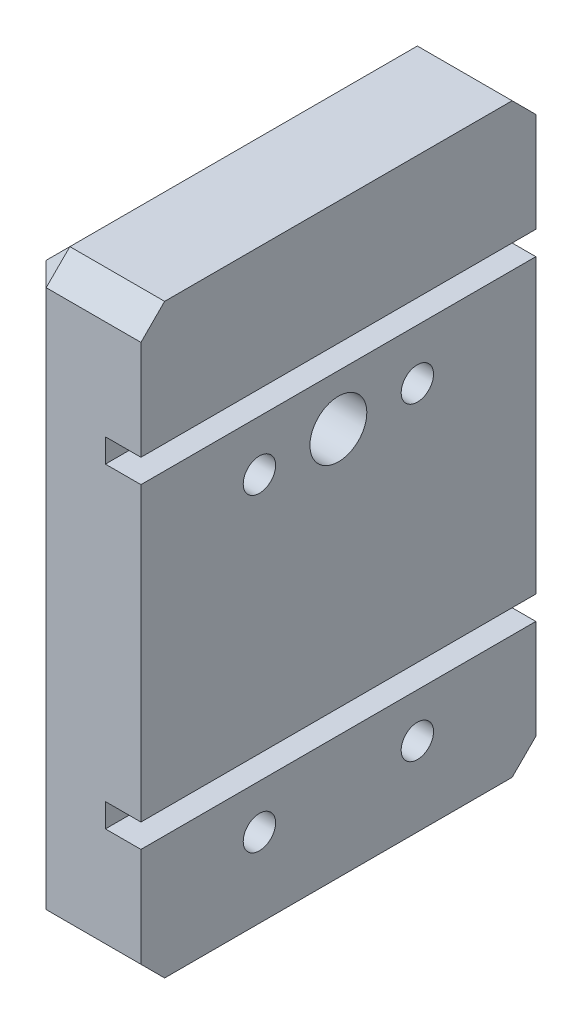
SolidWorks part; units mm, degrees
ref_plane "Front Plane" through (0, 0, 0) normal (0, 0, 1) x (1, 0, 0)
ref_plane "Top Plane" through (0, 0, 0) normal (0, 1, 0) x (1, 0, 0)
ref_plane "Right Plane" through (0, 0, 0) normal (1, 0, 0) x (0, 0, -1)
sketch "Sketch1" plane through (0, 0, 0) normal (0, 0, 1) x (1, 0, 0)
  line L2 (0, 0) -> (0, -74.2)
  line L10 (-15, -74.2) -> (-15, 0)
  line L12 (-15, 0) -> (0, 0)
  line L13 (0, -74.2) -> (-15, -74.2)
  point P0 (0, 0)
  dimension "D1" = 15
  dimension "D2" = 74.2
extrude "Boss-Extrude1" add sketch "Sketch1" along normal blind 50
sketch "Sketch4" plane through (-15, 0, 0) normal (-1, 0, 0) x (0, 0, 1)
  line L0 (0, 0) -> (50, -50) construction
  line L1 (50, 0) -> (50, -74.2) construction
  line L3 (50, 0) -> (0, 0) construction
  circle A0 centre (25, -25) radius 18 construction
  circle A1 centre (43, -25) radius 2.5
  circle A2 centre (41.2174, -32.8099) radius 2.5
  circle A3 centre (36.2228, -39.073) radius 2.5
  circle A4 centre (29.0054, -42.5487) radius 2.5
  circle A5 centre (20.9946, -42.5487) radius 2.5
  circle A6 centre (13.7772, -39.073) radius 2.5
  circle A7 centre (8.7826, -32.8099) radius 2.5
  circle A8 centre (7, -25) radius 2.5
  circle A9 centre (8.7826, -17.1901) radius 2.5
  circle A10 centre (13.7772, -10.927) radius 2.5
  circle A11 centre (20.9946, -7.4513) radius 2.5
  circle A12 centre (29.0054, -7.4513) radius 2.5
  circle A13 centre (36.2228, -10.927) radius 2.5
  circle A14 centre (41.2174, -17.1901) radius 2.5
  dimension "D2" = 5
  dimension "D4" = 36
  dimension "D1" = 45
  dimension "D5" = 25.714
  dimension "D3" = 14
extrude "Cut-Extrude4" cut sketch "Sketch4" against normal blind 4
chamfer "Chamfer2" distance 0.8 angle 45 14 edges at (-15, -27.5, 43) (-15, -19.6901, 41.2174) (-15, -13.427, 36.2228) (-15, -9.9513, 29.0054) (-15, -9.9513, 20.9946) (-15, -13.427, 13.7772) (-15, -19.6901, 8.7826) (-15, -27.5, 7) (-15, -35.3099, 8.7826) (-15, -41.573, 13.7772) (-15, -45.0487, 20.9946) (-15, -45.0487, 29.0054) (-15, -35.3099, 41.2174) (-15, -41.573, 36.2228)
sketch "Sketch5" plane through (-15, 0, 0) normal (-1, 0, 0) x (0, 0, 1)
  line L0 (13.7772, -39.073) -> (36.2228, -10.927) construction
  circle A0 centre (25, -25) radius 3.6
  dimension "D1" = 7.2
extrude "Cut-Extrude5" cut sketch "Sketch5" against normal up to surface (15 mm away) up to face at (0, -37.1, 25)
chamfer "Chamfer3" distance 1.5 angle 45 1 edges at (-15, -28.6, 25)
sketch "Sketch6" plane through (0, 0, 50) normal (0, 0, 1) x (1, 0, 0)
  line L0 (0, -74.2) -> (0, 0) construction
  line L1 (0, -15.6) -> (-4.5, -15.6)
  line L2 (0, -15.6) -> (0, -18.6)
  line L3 (0, -18.6) -> (-4.5, -18.6)
  line L4 (-4.5, -15.6) -> (-4.5, -18.6)
  line L9 (0, -37.1) -> (-15, -37.1) construction
  line L10 (-15, 0) -> (-15, -74.2) construction
  line L15 (-4.5, -58.6) -> (-4.5, -55.6)
  line L16 (0, -55.6) -> (-4.5, -55.6)
  line L17 (0, -58.6) -> (0, -55.6)
  line L18 (0, -58.6) -> (-4.5, -58.6)
  point P4 (-4.5, -17.1)
  point P5 (-4.5, -57.1)
  dimension "D1" = 3
  dimension "D2" = 40
  dimension "D3" = 4.5
extrude "Cut-Extrude6" cut sketch "Sketch6" against normal up to surface (50 mm away) up to face at (-7.5, -37.1, 0)
sketch "Sketch7" plane through (-15, 0, 0) normal (-1, 0, 0) x (0, 0, 1)
  line L0 (25, -35.2) -> (25, -74.2) construction
  line L1 (50, -74.2) -> (0, -74.2) construction
  line L2 (25, -25) -> (50, -25) construction
  line L3 (50, 0) -> (50, -74.2) construction
  circle A0 centre (15, -64.2) radius 3.75
  circle A1 centre (35, -64.2) radius 3.75
  circle A3 centre (15, -25) radius 3.75
  circle A4 centre (35, -25) radius 3.75
  point P18 (0, 0)
  point P19 (0, 0)
  point P20 (0, 0)
  dimension "D1" = 7.5
  dimension "D3" = 10
  dimension "D2" = 20
  dimension "D4" = 10
  dimension "D5" = 39.2
extrude "Cut-Extrude7" cut sketch "Sketch7" against normal blind 5
sketch "Sketch8" plane through (-10, 0, 0) normal (-1, 0, 0) x (0, 0, 1)
  circle A0 centre (35, -64.2) radius 2.05
  circle A1 centre (15, -64.2) radius 2.05
  circle A3 centre (15, -25) radius 2.05
  circle A4 centre (35, -25) radius 2.05
  dimension "D1" = 4.1
extrude "Cut-Extrude8" cut sketch "Sketch8" against normal up to surface (10 mm away) up to face at (0, -28.6, 25)
chamfer "Chamfer4" distance 3 angle 45 8 edges at (-7.5, 0, 0) (-7.5, 0, 50) (-7.5, -74.2, 0) (-7.5, -74.2, 50) (-15, 0, 25) (-15, -37.1, 50) (-15, -74.2, 25) (-15, -37.1, 0)
equation "\"diam\"=7.8"
